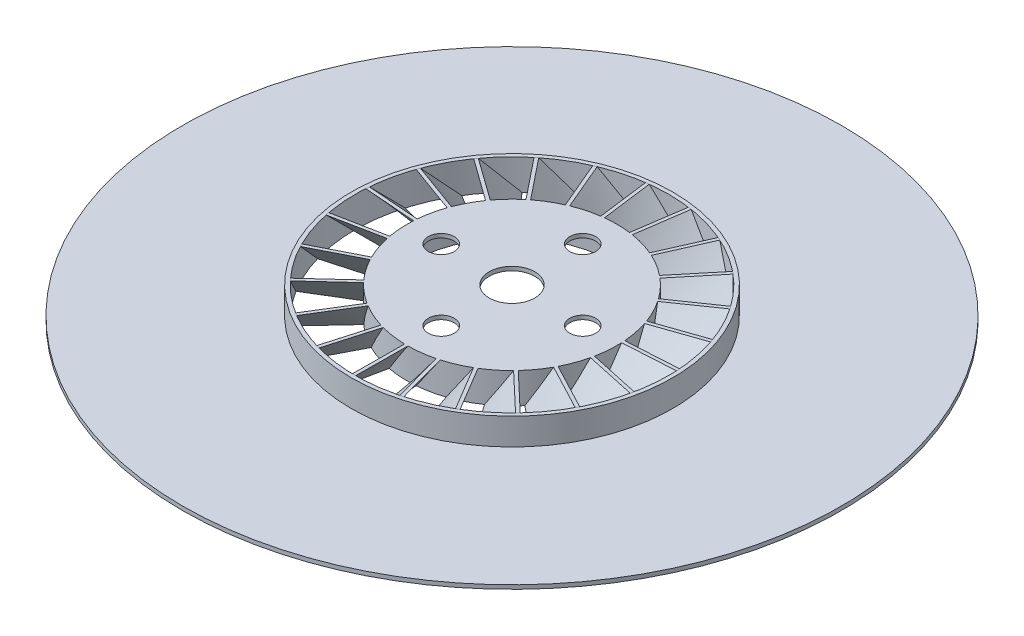
SolidWorks part; units mm, degrees
ref_plane "Front Plane" through (0, 0, 0) normal (0, 0, 1) x (1, 0, 0)
ref_plane "Top Plane" through (0, 0, 0) normal (0, 1, 0) x (1, 0, 0)
ref_plane "Right Plane" through (0, 0, 0) normal (1, 0, 0) x (0, 0, -1)
sketch "Sketch1" plane through (0, 0, 0) normal (0, 1, 0) x (1, 0, 0)
  circle A0 centre (0, 0) radius 33.25
  circle A1 centre (0, 0) radius 34.0882
  circle A2 centre (0, 0) radius 69.85
  circle A3 centre (0, 0) radius 22.25
  circle A4 centre (0, 0) radius 21.4118
  dimension "D1" = 66.5
  dimension "D2" = 0.8382
  dimension "D3" = 139.7
  dimension "D4" = 44.5
  dimension "D5" = 0.8382
extrude "Boss-Extrude1" add sketch "Sketch1" along normal blind 6.5 contours A1 A0 region at (-33.9918, 0, 0)
extrude "Boss-Extrude2" add sketch "Sketch1<3>" along normal blind 0.8382 contours A2 A1 region at (-67.8743, 0, 0)
sketch "Sketch1<3>" plane through (0, 0, 0) normal (0, 1, 0) x (1, 0, 0) same geometry as "Sketch1"
extrude "Boss-Extrude3" add sketch "Sketch1<4>" along normal blind 6.5 separate body contours A3 A4 region at (-21.6207, 0, 0)
sketch "Sketch1<4>" plane through (0, 0, 0) normal (0, 1, 0) x (1, 0, 0) same geometry as "Sketch1"
extrude "Boss-Extrude4" add sketch "Sketch1<5>" along normal blind 0.7 contours A4 region at (0, 0, 0)
sketch "Sketch1<5>" plane through (0, 0, 0) normal (0, 1, 0) x (1, 0, 0) same geometry as "Sketch1"
sketch "Sketch2" plane through (0, 0, 0) normal (0, -1, 0) x (1, 0, 0)
  line L0 (-31.9208, 9.3073) -> (-21.3278, 6.3393)
  line L1 (-33.2482, 0.35) -> (-22.2472, 0.35)
  line L2 (-33.2482, -0.35) -> (-22.2472, -0.35)
  line L3 (-32.1097, 8.6332) -> (-21.5167, 5.6652)
  line L4 (-28.226, 17.5743) -> (-18.8266, 11.8584)
  line L5 (-28.5897, 16.9762) -> (-19.1903, 11.2603)
  line L6 (-22.4378, 24.5378) -> (-14.9291, 16.498)
  line L7 (-22.9494, 24.0601) -> (-15.4407, 16.0202)
  line L8 (-14.9856, 29.6816) -> (-9.9244, 19.914)
  line L9 (-15.6071, 29.3595) -> (-10.5459, 19.592)
  line L10 (-6.4219, 32.624) -> (-4.1837, 21.8531)
  line L11 (-7.1072, 32.4815) -> (-4.869, 21.7107)
  line L12 (2.6181, 33.1468) -> (1.8674, 22.1715)
  line L13 (1.9198, 33.1945) -> (1.169, 22.2193)
  line L14 (11.4639, 31.2112) -> (7.7799, 20.8455)
  line L15 (10.8043, 31.4456) -> (7.1204, 21.0799)
  line L16 (19.4595, 26.9609) -> (13.1155, 17.9735)
  line L17 (18.8876, 27.3646) -> (12.5436, 18.3772)
  line L18 (26.0119, 20.711) -> (17.4783, 13.7685)
  line L19 (25.5701, 21.254) -> (17.0366, 14.3115)
  line L20 (30.635, 12.9251) -> (20.5449, 8.5423)
  line L21 (30.3561, 13.5671) -> (20.266, 9.1844)
  line L22 (32.9861, 4.1806) -> (22.0877, 2.6826)
  line L23 (32.8908, 4.874) -> (21.9924, 3.3761)
  line L24 (32.8908, -4.874) -> (21.9924, -3.3761)
  line L25 (32.9861, -4.1806) -> (22.0877, -2.6826)
  line L26 (30.3561, -13.5671) -> (20.266, -9.1844)
  line L27 (30.635, -12.9251) -> (20.5449, -8.5423)
  line L28 (25.5701, -21.254) -> (17.0366, -14.3115)
  line L29 (26.0119, -20.711) -> (17.4783, -13.7685)
  line L30 (18.8876, -27.3646) -> (12.5436, -18.3772)
  line L31 (19.4595, -26.9609) -> (13.1155, -17.9735)
  line L32 (10.8043, -31.4456) -> (7.1204, -21.0799)
  line L33 (11.4639, -31.2112) -> (7.7799, -20.8455)
  line L34 (1.9198, -33.1945) -> (1.169, -22.2193)
  line L35 (2.6181, -33.1468) -> (1.8674, -22.1715)
  line L36 (-7.1072, -32.4815) -> (-4.869, -21.7107)
  line L37 (-6.4219, -32.624) -> (-4.1837, -21.8531)
  line L38 (-15.6071, -29.3595) -> (-10.5459, -19.592)
  line L39 (-14.9856, -29.6816) -> (-9.9244, -19.914)
  line L40 (-22.9494, -24.0601) -> (-15.4407, -16.0202)
  line L41 (-22.4378, -24.5378) -> (-14.9291, -16.498)
  line L42 (-28.5897, -16.9762) -> (-19.1903, -11.2603)
  line L43 (-28.226, -17.5743) -> (-18.8266, -11.8584)
  line L44 (-32.1097, -8.6332) -> (-21.5167, -5.6652)
  line L45 (-31.9208, -9.3073) -> (-21.3278, -6.3393)
  circle A0 centre (0, 0) radius 33.25 construction
  circle A1 centre (0, 0) radius 22.25
  arc A2 (-21.3278, 6.3393) -> (-21.5167, 5.6652) centre (0, 0) ccw
  arc A3 (-18.8266, 11.8584) -> (-19.1903, 11.2603) centre (0, 0) ccw
  circle A5 centre (0, 0) radius 22.25 construction
  arc A6 (-31.9208, 9.3073) -> (-32.1097, 8.6332) centre (0, 0) ccw
  arc A7 (-28.226, 17.5743) -> (-28.5897, 16.9762) centre (0, 0) ccw
  arc A8 (-22.4378, 24.5378) -> (-22.9494, 24.0601) centre (0, 0) ccw
  arc A9 (-14.9291, 16.498) -> (-15.4407, 16.0202) centre (0, 0) ccw
  arc A10 (-9.9244, 19.914) -> (-10.5459, 19.592) centre (0, 0) ccw
  arc A11 (-14.9856, 29.6816) -> (-15.6071, 29.3595) centre (0, 0) ccw
  arc A12 (-6.4219, 32.624) -> (-7.1072, 32.4815) centre (0, 0) ccw
  arc A13 (-4.1837, 21.8531) -> (-4.869, 21.7107) centre (0, 0) ccw
  arc A14 (1.8674, 22.1715) -> (1.169, 22.2193) centre (0, 0) ccw
  arc A15 (2.6181, 33.1468) -> (1.9198, 33.1945) centre (0, 0) ccw
  arc A16 (11.4639, 31.2112) -> (10.8043, 31.4456) centre (0, 0) ccw
  arc A17 (7.7799, 20.8455) -> (7.1204, 21.0799) centre (0, 0) ccw
  arc A18 (13.1155, 17.9735) -> (12.5436, 18.3772) centre (0, 0) ccw
  arc A19 (19.4595, 26.9609) -> (18.8876, 27.3646) centre (0, 0) ccw
  arc A20 (26.0119, 20.711) -> (25.5701, 21.254) centre (0, 0) ccw
  arc A21 (17.4783, 13.7685) -> (17.0366, 14.3115) centre (0, 0) ccw
  arc A22 (20.5449, 8.5423) -> (20.266, 9.1844) centre (0, 0) ccw
  arc A23 (30.635, 12.9251) -> (30.3561, 13.5671) centre (0, 0) ccw
  arc A24 (32.9861, 4.1806) -> (32.8908, 4.874) centre (0, 0) ccw
  arc A25 (22.0877, 2.6826) -> (21.9924, 3.3761) centre (0, 0) ccw
  arc A26 (21.9924, -3.3761) -> (22.0877, -2.6826) centre (0, 0) ccw
  arc A27 (32.8908, -4.874) -> (32.9861, -4.1806) centre (0, 0) ccw
  arc A28 (-22.2472, 0.35) -> (-22.2472, -0.35) centre (0, 0) ccw
  arc A29 (-33.2482, 0.35) -> (-33.2482, -0.35) centre (0, 0) ccw
  arc A30 (-21.5167, -5.6652) -> (-21.3278, -6.3393) centre (0, 0) ccw
  arc A31 (-32.1097, -8.6332) -> (-31.9208, -9.3073) centre (0, 0) ccw
  arc A32 (-19.1903, -11.2603) -> (-18.8266, -11.8584) centre (0, 0) ccw
  arc A33 (-28.5897, -16.9762) -> (-28.226, -17.5743) centre (0, 0) ccw
  arc A34 (-22.9494, -24.0601) -> (-22.4378, -24.5378) centre (0, 0) ccw
  arc A35 (-15.4407, -16.0202) -> (-14.9291, -16.498) centre (0, 0) ccw
  arc A36 (-10.5459, -19.592) -> (-9.9244, -19.914) centre (0, 0) ccw
  arc A37 (-15.6071, -29.3595) -> (-14.9856, -29.6816) centre (0, 0) ccw
  arc A38 (-7.1072, -32.4815) -> (-6.4219, -32.624) centre (0, 0) ccw
  arc A39 (-4.869, -21.7107) -> (-4.1837, -21.8531) centre (0, 0) ccw
  arc A40 (1.169, -22.2193) -> (1.8674, -22.1715) centre (0, 0) ccw
  arc A41 (1.9198, -33.1945) -> (2.6181, -33.1468) centre (0, 0) ccw
  arc A42 (10.8043, -31.4456) -> (11.4639, -31.2112) centre (0, 0) ccw
  arc A43 (7.1204, -21.0799) -> (7.7799, -20.8455) centre (0, 0) ccw
  arc A44 (12.5436, -18.3772) -> (13.1155, -17.9735) centre (0, 0) ccw
  arc A45 (18.8876, -27.3646) -> (19.4595, -26.9609) centre (0, 0) ccw
  arc A46 (25.5701, -21.254) -> (26.0119, -20.711) centre (0, 0) ccw
  arc A47 (17.0366, -14.3115) -> (17.4783, -13.7685) centre (0, 0) ccw
  arc A48 (20.266, -9.1844) -> (20.5449, -8.5423) centre (0, 0) ccw
  arc A49 (30.3561, -13.5671) -> (30.635, -12.9251) centre (0, 0) ccw
  point P106 (0, 0)
  dimension "D3" = 0.7
  dimension "D1" = 0
  dimension "D4" = 23
sketch "Sketch3" plane through (0, 6.5, 0) normal (0, 1, 0) x (1, 0, 0)
  line L0 (0, 0) -> (-32.6054, -6.5152) construction
  line L1 (0, 0) -> (-15.6581, 0) construction
  line L2 (-21.8846, -4.016) -> (-32.6722, -6.1716)
  line L3 (-21.7474, -4.7025) -> (-32.535, -6.8581)
  line L4 (-22.1565, 2.0373) -> (-33.1257, 2.8721)
  line L5 (-22.2097, 1.3393) -> (-33.1788, 2.1741)
  line L6 (-20.7853, 7.9395) -> (-31.1225, 11.7028)
  line L7 (-21.0247, 7.2817) -> (-31.3619, 11.045)
  line L8 (-17.8724, 13.2529) -> (-26.811, 19.6656)
  line L9 (-18.2805, 12.6841) -> (-27.219, 19.0968)
  line L10 (-13.6341, 17.5833) -> (-20.511, 26.1698)
  line L11 (-14.1805, 17.1457) -> (-21.0574, 25.7322)
  line L12 (-8.3846, 20.6097) -> (-12.6899, 30.7332)
  line L13 (-9.0288, 20.3358) -> (-13.3341, 30.4592)
  line L14 (-2.5132, 22.1076) -> (-3.9276, 33.0172)
  line L15 (-3.2074, 22.0176) -> (-4.6218, 32.9272)
  line L16 (3.5445, 21.9659) -> (5.126, 32.8525)
  line L17 (2.8518, 22.0665) -> (4.4332, 32.9531)
  line L18 (9.3394, 20.195) -> (13.7994, 30.2513)
  line L19 (8.6995, 20.4788) -> (13.1595, 30.5351)
  line L20 (14.4416, 16.9264) -> (21.4494, 25.4064)
  line L21 (13.902, 17.3723) -> (20.9098, 25.8524)
  line L22 (18.4728, 12.4024) -> (27.5085, 18.6773)
  line L23 (18.0735, 12.9774) -> (27.1093, 19.2523)
  line L24 (21.1339, 6.9586) -> (31.5275, 10.563)
  line L25 (20.9045, 7.6199) -> (31.2982, 11.2244)
  line L26 (22.2276, 0.9987) -> (33.2083, 1.6653)
  line L27 (22.1852, 1.6974) -> (33.1659, 2.364)
  line L28 (21.6728, -5.0353) -> (32.4261, -7.356)
  line L29 (21.8204, -4.351) -> (32.5738, -6.6717)
  line L30 (19.5106, -10.6958) -> (29.239, -15.8316)
  line L31 (19.8374, -10.0768) -> (29.5658, -15.2126)
  line L32 (15.9014, -15.563) -> (23.8835, -23.1332)
  line L33 (16.3831, -15.0551) -> (24.3652, -22.6252)
  line L34 (11.1129, -19.2761) -> (16.7565, -28.719)
  line L35 (11.7137, -18.917) -> (17.3574, -28.3599)
  line L36 (5.5001, -21.5595) -> (8.3869, -32.1749)
  line L37 (6.1756, -21.3758) -> (9.0623, -31.9912)
  line L38 (-0.5205, -22.2439) -> (-0.6048, -33.2445)
  line L39 (0.1795, -22.2493) -> (0.0952, -33.2499)
  line L40 (-6.5025, -21.2786) -> (-9.5516, -31.8485)
  line L41 (-5.83, -21.4726) -> (-8.8791, -32.0425)
  line L42 (-12.0023, -18.7352) -> (-17.7901, -28.0905)
  line L43 (-11.407, -19.1035) -> (-17.1948, -28.4588)
  line L44 (-16.6119, -14.8023) -> (-24.7091, -22.2491)
  line L45 (-16.1381, -15.3175) -> (-24.2352, -22.7644)
  line L46 (-19.9895, -9.7715) -> (-29.7956, -14.7576)
  line L47 (-19.6722, -10.3955) -> (-29.4783, -15.3816)
  circle A0 centre (0, 0) radius 33.25 construction
  circle A1 centre (0, 0) radius 22.25 construction
  arc A2 (-32.6722, -6.1716) -> (-32.535, -6.8581) centre (0, 0) ccw
  arc A3 (-21.8846, -4.016) -> (-21.7474, -4.7025) centre (0, 0) ccw
  arc A4 (-22.1565, 2.0373) -> (-22.2097, 1.3393) centre (0, 0) ccw
  arc A5 (-33.1257, 2.8721) -> (-33.1788, 2.1741) centre (0, 0) ccw
  arc A6 (-20.7853, 7.9395) -> (-21.0247, 7.2817) centre (0, 0) ccw
  arc A7 (-31.1225, 11.7028) -> (-31.3619, 11.045) centre (0, 0) ccw
  arc A8 (-17.8724, 13.2529) -> (-18.2805, 12.6841) centre (0, 0) ccw
  arc A9 (-26.811, 19.6656) -> (-27.219, 19.0968) centre (0, 0) ccw
  arc A10 (-13.6341, 17.5833) -> (-14.1805, 17.1457) centre (0, 0) ccw
  arc A11 (-20.511, 26.1698) -> (-21.0574, 25.7322) centre (0, 0) ccw
  arc A12 (-8.3846, 20.6097) -> (-9.0288, 20.3358) centre (0, 0) ccw
  arc A13 (-12.6899, 30.7332) -> (-13.3341, 30.4592) centre (0, 0) ccw
  arc A14 (-2.5132, 22.1076) -> (-3.2074, 22.0176) centre (0, 0) ccw
  arc A15 (-3.9276, 33.0172) -> (-4.6218, 32.9272) centre (0, 0) ccw
  arc A16 (3.5445, 21.9659) -> (2.8518, 22.0665) centre (0, 0) ccw
  arc A17 (5.126, 32.8525) -> (4.4332, 32.9531) centre (0, 0) ccw
  arc A18 (9.3394, 20.195) -> (8.6995, 20.4788) centre (0, 0) ccw
  arc A19 (13.7994, 30.2513) -> (13.1595, 30.5351) centre (0, 0) ccw
  arc A20 (14.4416, 16.9264) -> (13.902, 17.3723) centre (0, 0) ccw
  arc A21 (21.4494, 25.4064) -> (20.9098, 25.8524) centre (0, 0) ccw
  arc A22 (18.4728, 12.4024) -> (18.0735, 12.9774) centre (0, 0) ccw
  arc A23 (27.5085, 18.6773) -> (27.1093, 19.2523) centre (0, 0) ccw
  arc A24 (21.1339, 6.9586) -> (20.9045, 7.6199) centre (0, 0) ccw
  arc A25 (31.5275, 10.563) -> (31.2982, 11.2244) centre (0, 0) ccw
  arc A26 (22.2276, 0.9987) -> (22.1852, 1.6974) centre (0, 0) ccw
  arc A27 (33.2083, 1.6653) -> (33.1659, 2.364) centre (0, 0) ccw
  arc A28 (21.6728, -5.0353) -> (21.8204, -4.351) centre (0, 0) ccw
  arc A29 (32.4261, -7.356) -> (32.5738, -6.6717) centre (0, 0) ccw
  arc A30 (19.5106, -10.6958) -> (19.8374, -10.0768) centre (0, 0) ccw
  arc A31 (29.239, -15.8316) -> (29.5658, -15.2126) centre (0, 0) ccw
  arc A32 (15.9014, -15.563) -> (16.3831, -15.0551) centre (0, 0) ccw
  arc A33 (23.8835, -23.1332) -> (24.3652, -22.6252) centre (0, 0) ccw
  arc A34 (11.1129, -19.2761) -> (11.7137, -18.917) centre (0, 0) ccw
  arc A35 (16.7565, -28.719) -> (17.3574, -28.3599) centre (0, 0) ccw
  arc A36 (5.5001, -21.5595) -> (6.1756, -21.3758) centre (0, 0) ccw
  arc A37 (8.3869, -32.1749) -> (9.0623, -31.9912) centre (0, 0) ccw
  arc A38 (-0.5205, -22.2439) -> (0.1795, -22.2493) centre (0, 0) ccw
  arc A39 (-0.6048, -33.2445) -> (0.0952, -33.2499) centre (0, 0) ccw
  arc A40 (-6.5025, -21.2786) -> (-5.83, -21.4726) centre (0, 0) ccw
  arc A41 (-9.5516, -31.8485) -> (-8.8791, -32.0425) centre (0, 0) ccw
  arc A42 (-12.0023, -18.7352) -> (-11.407, -19.1035) centre (0, 0) ccw
  arc A43 (-17.7901, -28.0905) -> (-17.1948, -28.4588) centre (0, 0) ccw
  arc A44 (-16.6119, -14.8023) -> (-16.1381, -15.3175) centre (0, 0) ccw
  arc A45 (-24.7091, -22.2491) -> (-24.2352, -22.7644) centre (0, 0) ccw
  arc A46 (-19.9895, -9.7715) -> (-19.6722, -10.3955) centre (0, 0) ccw
  arc A47 (-29.7956, -14.7576) -> (-29.4783, -15.3816) centre (0, 0) ccw
  point P101 (0, 0)
  dimension "D1" = 11.3
  dimension "D2" = 0.35
  dimension "D3" = 0.35
  dimension "D4" = 23
loft "Loft1" add section "Sketch2" section "Sketch3" connector at (-32.1097, 0, 8.6332) connector at (-29.7956, 6.5, 14.7576)
pattern_circular "CirPattern1" count 23 over 360 about axis through (0, 6.5, 0) along (0, -1, 0) of "Loft1"
sketch "Sketch4" plane through (0, 6.5, 0) normal (0, 1, 0) x (1, 0, 0)
  circle A0 centre (0, 0) radius 21.55
  dimension "D1" = 43.1
extrude "Boss-Extrude5" add sketch "Sketch4" against normal blind 0.8382
sketch "Sketch6" plane through (0, 0, 0) normal (0, -1, 0) x (1, 0, 0)
  line L0 (0, 0) -> (0, 14.9949) construction
  line L1 (0, 0) -> (14.9949, 0) construction
  line L2 (0, 0) -> (0, -14.9949) construction
  line L3 (0, 0) -> (-14.9949, 0) construction
  point P9 (0, 0)
  dimension "D1" = 14.9949
  dimension "D2" = 4
hole_wizard "CBORE for M5 Hex Head Bolt1" positions "3DSketch4" profile "Sketch7" counterbore size "M5" standard "ANSI Metric" end condition through all
sketch3d "3DSketch4"
  point P0 (0, 0, 14.9949)
  point P3 (14.9949, 0, 0)
  point P6 (0, 0, -14.9949)
  point P9 (-14.9949, 0, 0)
sketch "Sketch7" plane through (0, 0, 14.9949) normal (1, 0, 0) x (0, 0, -1)
  line L0 (0, 0) -> (0, 6.5001)
  line L1 (0, 6.5001) -> (2.75, 6.5001)
  line L3 (2.75, 6.5001) -> (2.75, 3.58)
  line L4 (2.75, 3.58) -> (6.12, 3.58)
  line L5 (6.12, 3.58) -> (6.12, 0)
  line L7 (6.12, 0) -> (0, 0)
  line L11 (0, -6.35) -> (0, 107.95) construction
  dimension "Thru Hole Dia." = 5.5
  dimension "Thru Hole Depth" = 6.5001
  dimension "C'Bore Dia." = 12.24
  dimension "C'Bore Depth" = 3.58
sketch "Sketch8" plane through (0, 0, 0) normal (0, -1, 0) x (1, 0, 0)
  circle A0 centre (0, 0) radius 21.39
  arc A1 (22.0877, -2.6826) -> (22.0877, 2.6826) centre (0, 0) ccw construction
  circle A2 centre (0, 0) radius 22.25
  dimension "D1" = 0.86
  dimension "D2" = 44.5
extrude "Cut-Extrude1" cut sketch "Sketch8" against normal blind 1.5 contours A0 region at (0, 0, 0)
extrude "Boss-Extrude6" add sketch "Sketch8<2>" against normal up to surface (6.5 mm away) up to face at (0, 6.5, 17.7449)
sketch "Sketch8<2>" plane through (0, 0, 0) normal (0, -1, 0) x (1, 0, 0) same geometry as "Sketch8"
sketch "Sketch9" plane through (0, 5.6618, 0) normal (0, -1, 0) x (1, 0, 0)
  circle A0 centre (0, 0) radius 4.826
  dimension "D1" = 9.652
extrude "Cut-Extrude3" cut sketch "Sketch9" against normal blind 2.54
